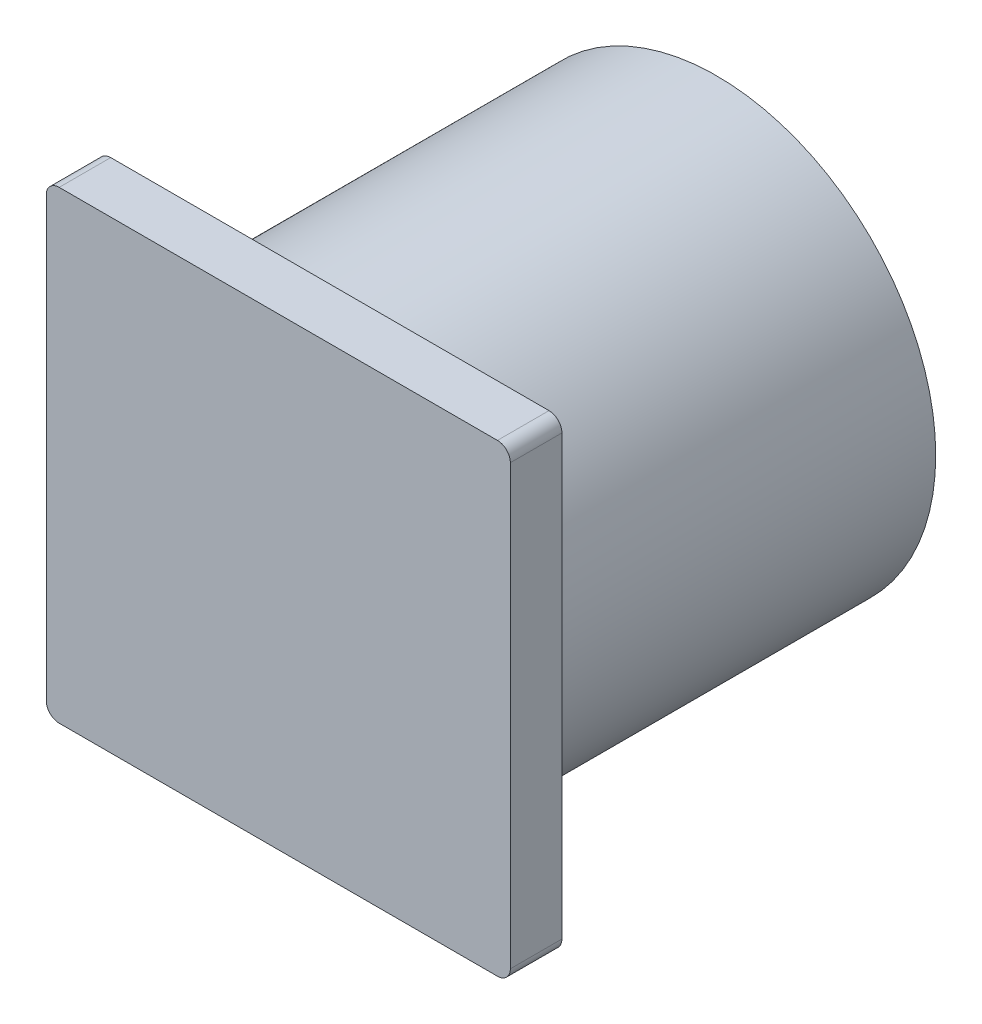
SolidWorks part; units mm, degrees
material "3.0205 (EN-AW 1200)"
ref_plane "Plan de face" through (0, 0, 0) normal (0, 0, 1) x (1, 0, 0)
ref_plane "Plan de dessus" through (0, 0, 0) normal (0, 1, 0) x (1, 0, 0)
ref_plane "Plan de droite" through (0, 0, 0) normal (1, 0, 0) x (0, 0, -1)
sketch "Esquisse1" plane through (0, 0, 0) normal (0, 0, 1) x (1, 0, 0)
  circle A0 centre (0, 0) radius 85
  dimension "D1" = 170
extrude "Boss.-Extru.1" add sketch "Esquisse1" along normal blind 150
sketch "Esquisse2" plane through (0, 0, 150) normal (0, 0, 1) x (1, 0, 0)
  line L0 (-110.1154, 0) -> (117.3282, 0) construction
  line L1 (-90, 90) -> (90, 90)
  line L2 (-90, 90) -> (-90, -90)
  line L3 (-90, -90) -> (90, -90)
  line L4 (90, 90) -> (90, -90)
  line L5 (0, 101.9602) -> (0, -123.0793) construction
  dimension "D1" = 180
  dimension "D2" = 180
extrude "Boss.-Extru.2" add sketch "Esquisse2" along normal blind 20
fillet "Congé1" radius 5 1 edges at (85, 0, 150)
fillet "Congé2" radius 5 1 edges at (-90, 90, 160)
fillet "Congé3" radius 5 1 edges at (-90, -90, 160)
fillet "Congé4" radius 5 1 edges at (90, 90, 160)
fillet "Congé5" radius 5 1 edges at (90, -90, 160)
sketch "Esquisse3" plane through (0, 0, 0) normal (0, 0, -1) x (-1, 0, 0)
  line L0 (0, 0) -> (0, 180.7973)
curve "Courbe1"
  spline degree 1 poles (100, 0, -100) (300, 0, -100) knots 0 0 1 1
ref_plane "Plan1" through (100, 0, 0) normal (1, 0, 0) x (0, 0, -1)
